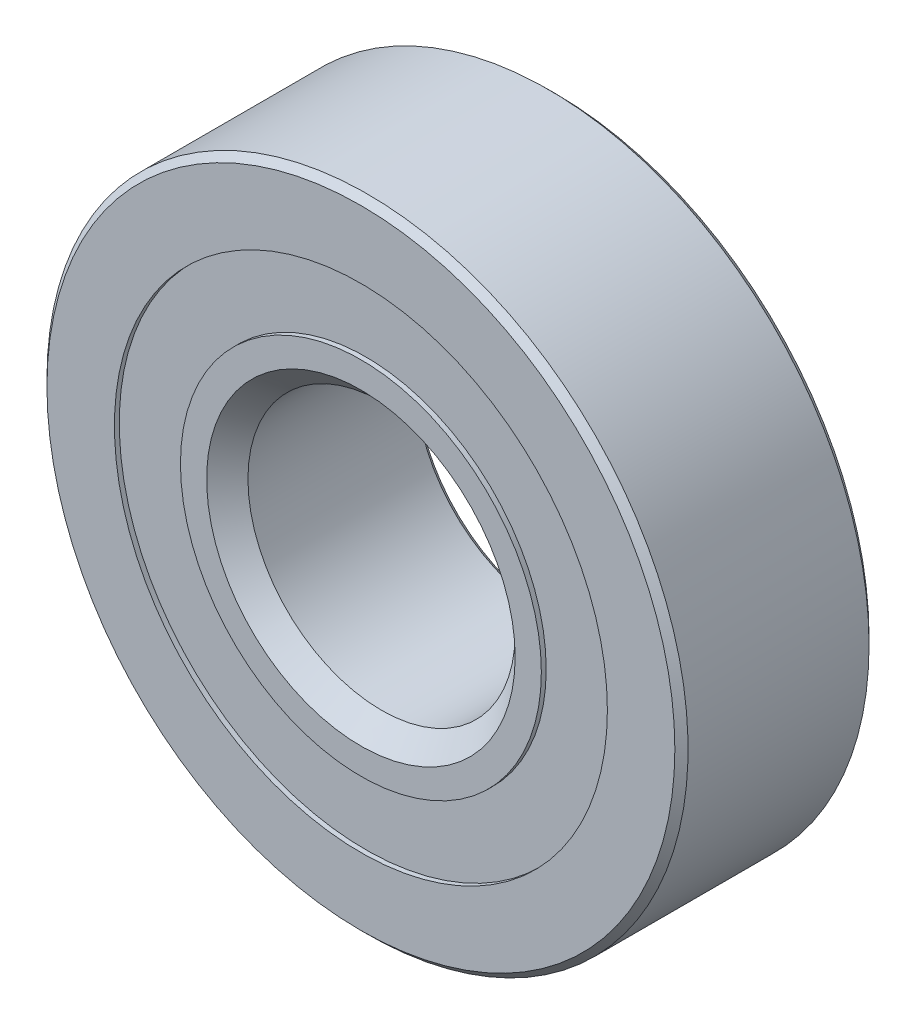
SolidWorks part; units mm, degrees
ref_plane "Front Plane" through (0, 0, 0) normal (0, 0, 1) x (1, 0, 0)
ref_plane "Top Plane" through (0, 0, 0) normal (0, 1, 0) x (1, 0, 0)
ref_plane "Right Plane" through (0, 0, 0) normal (1, 0, 0) x (0, 0, -1)
sketch "Sketch1" plane through (0, 0, 0) normal (1, 0, 0) x (0, 0, -1)
  line L0 (-2.3813, 0) -> (2.3813, 0) construction
  line L1 (0, 7.9375) -> (0, -7.9375) construction
  line L2 (2.1431, 7.9375) -> (-2.1431, 7.9375)
  line L3 (-2.1431, 7.9375) -> (-2.3813, 7.6994)
  line L4 (-2.3813, 7.6994) -> (-2.3813, 6.0447)
  line L5 (-2.3813, 6.0447) -> (-1.0583, 6.0447)
  line L6 (2.3813, 6.0447) -> (1.0583, 6.0447)
  line L7 (2.3813, 7.6994) -> (2.3813, 6.0447)
  line L8 (2.1431, 7.9375) -> (2.3813, 7.6994)
  line L9 (0, 7.9375) -> (0, 5.5563) construction
  line L10 (0, 5.5563) -> (0, 3.175) construction
  arc A0 (-1.0583, 6.0447) -> (1.0583, 6.0447) centre (0, 5.5563) cw
  point P14 (0, 3.175)
  dimension "Width" = 4.7625
  dimension "OD" = 15.875
  dimension "D1" = 45
  dimension "D2" = 0.2381
  dimension "D3" = 2.1167
  dimension "D4" = 0.4885
revolve "Revolve1" add sketch "Sketch1" angle 360 about L0
sketch "Sketch2" plane through (0, 0, 0) normal (1, 0, 0) x (0, 0, -1)
  line L0 (-2.2622, 5.0678) -> (-1.0583, 5.0678)
  line L1 (-2.3813, 7.6994) -> (-2.3813, -7.6994) construction
  line L2 (-2.3813, 4.4253) -> (-2.2622, 4.4253) construction
  line L3 (-2.2622, 4.3062) -> (-1.7388, 3.7828)
  line L4 (-1.7388, 3.7828) -> (0, 3.7828)
  line L5 (0, 7.9375) -> (0, -7.9375) construction
  line L6 (0, 3.7828) -> (0, 4.3906)
  line L7 (0, 4.3906) -> (0, 3.175) construction
  line L8 (-2.3813, 5.0678) -> (-2.3813, 3.7828) construction
  line L9 (-2.3813, 3.7828) -> (-1.7388, 3.7828) construction
  line L10 (-2.2622, 5.0678) -> (-2.2622, 4.3062)
  line L11 (-2.2622, 5.0678) -> (-2.2622, 7.8184) construction
  line L12 (-2.1431, 7.9375) -> (-2.3813, 7.6994) construction
  arc A0 (-1.0583, 5.0678) -> (0, 4.3906) centre (0, 5.5563) ccw
  arc A1 (1.0583, 6.0447) -> (-1.0583, 6.0447) centre (0, 5.5563) ccw construction
  circle A2 centre (0, 5.5563) radius 1.1656 construction
  dimension "D1" = 45
revolve "Revolve2" [suppressed] add sketch "Sketch2" angle 360 about L0
sketch "Sketch3" plane through (0, 0, 0) normal (1, 0, 0) x (0, 0, -1)
  line L0 (-2.2622, 4.3062) -> (-1.7388, 3.7828)
  line L1 (-1.7388, 3.7828) -> (0, 3.7828)
  line L2 (0, 3.7828) -> (0, 4.3906)
  line L3 (-2.3813, 4.4253) -> (-2.3813, 3.7828)
  line L4 (-2.3813, 5.0678) -> (-2.3813, 3.7828) construction
  line L5 (-2.3813, 3.7828) -> (-1.7734, 3.175)
  line L6 (-1.7734, 3.175) -> (2.1431, 3.175)
  line L7 (2.1431, 7.9375) -> (2.1431, -7.9375) construction
  line L8 (2.1431, 3.175) -> (2.3812, 3.4131)
  line L9 (2.3813, -7.6994) -> (2.3813, 7.6994) construction
  line L10 (2.3812, 3.4131) -> (2.3813, 5.0678)
  line L11 (2.3813, 5.0678) -> (1.0583, 5.0678)
  line L12 (-2.3813, 4.4253) -> (-2.2622, 4.4253)
  line L13 (2.1431, 7.9375) -> (2.3813, 7.6994) construction
  line L14 (-2.2622, 4.4253) -> (-2.2622, 4.3062)
  circle A0 centre (0, 5.5563) radius 1.1656 construction
  arc A1 (1.0583, 5.0678) -> (0, 4.3906) centre (0, 5.5563) cw
revolve "Revolve3" add sketch "Sketch3" angle 360 about L0
sketch "Sketch4" plane through (0, 0, 0) normal (1, 0, 0) x (0, 0, -1)
  line L0 (-1.1656, 5.5563) -> (1.1656, 5.5563)
  circle A1 centre (0, 5.5563) radius 1.1656 construction
  arc A2 (-1.1656, 5.5563) -> (1.1656, 5.5563) centre (0, 5.5563) cw
  arc A3 (1.0583, 6.0447) -> (-1.0583, 6.0447) centre (0, 5.5563) ccw construction
revolve "Revolve4" add sketch "Sketch4" angle 360 about L0
ref_axis "Axis1" through (0, 0, -2.3813) along (0, 0, 1)
pattern_circular "CirPattern1" count 10 every 36 about axis through (0, 0, -2.3813) along (0, 0, 1) of bodies 104
sketch "Sketch5" plane through (0, 0, 0) normal (1, 0, 0) x (0, 0, -1)
  line L0 (-2.3813, 6.0447) -> (-1.0583, 6.0447) construction
  line L1 (-2.2622, 6.0447) -> (-1.1656, 6.0447)
  line L2 (-2.2622, 6.0447) -> (-2.2622, 4.4253)
  line L3 (-2.2622, 4.4253) -> (-1.1656, 4.4253)
  line L4 (-1.1656, 6.0447) -> (-1.1656, 4.4253)
  line L6 (-2.1431, 7.9375) -> (-2.3813, 7.6994) construction
  line L7 (0, 7.9375) -> (0, 3.175) construction
  line L8 (2.2622, 4.4253) -> (1.1656, 4.4253)
  line L9 (1.1656, 6.0447) -> (1.1656, 4.4253)
  line L10 (2.2622, 6.0447) -> (1.1656, 6.0447)
  line L11 (2.2622, 6.0447) -> (2.2622, 4.4253)
  circle A0 centre (0, 5.5563) radius 1.1656 construction
  point P10 (-2.2622, 7.8184)
revolve "Revolve5" add sketch "Sketch5" angle 360 about L0
sketch "Sketch6" plane through (0, 0, -2.3813) normal (0, 0, -1) x (-1, 0, 0)
  circle A0 centre (0, 0) radius 3.2766
  dimension "D1" = 6.5532
extrude "Cut-Extrude1" cut sketch "Sketch6" against normal blind 7.62
sketch "Sketch7" plane through (0, 0, -2.3813) normal (0, 0, -1) x (-1, 0, 0)
  circle A0 centre (0, 0) radius 8.001
  circle A1 centre (0, 0) radius 7.8613
  dimension "D1" = 15.7226
  dimension "D2" = 16.002
extrude "Cut-Extrude2" cut sketch "Sketch7" against normal blind 7.62
equation "\"D2@Sketch1\" = \"Width@Sketch1\"*.05"
equation "\"D3@Sketch1\" = \"Width@Sketch1\"/2.25"
equation "\"D4@Sketch1\" = (((\"OD@Sketch1\"-\"Width@Sketch1\")/2)/3.25)/3.5"
equation "\"D2@CirPattern1\" = 360/\"Balls@CirPattern1\""
